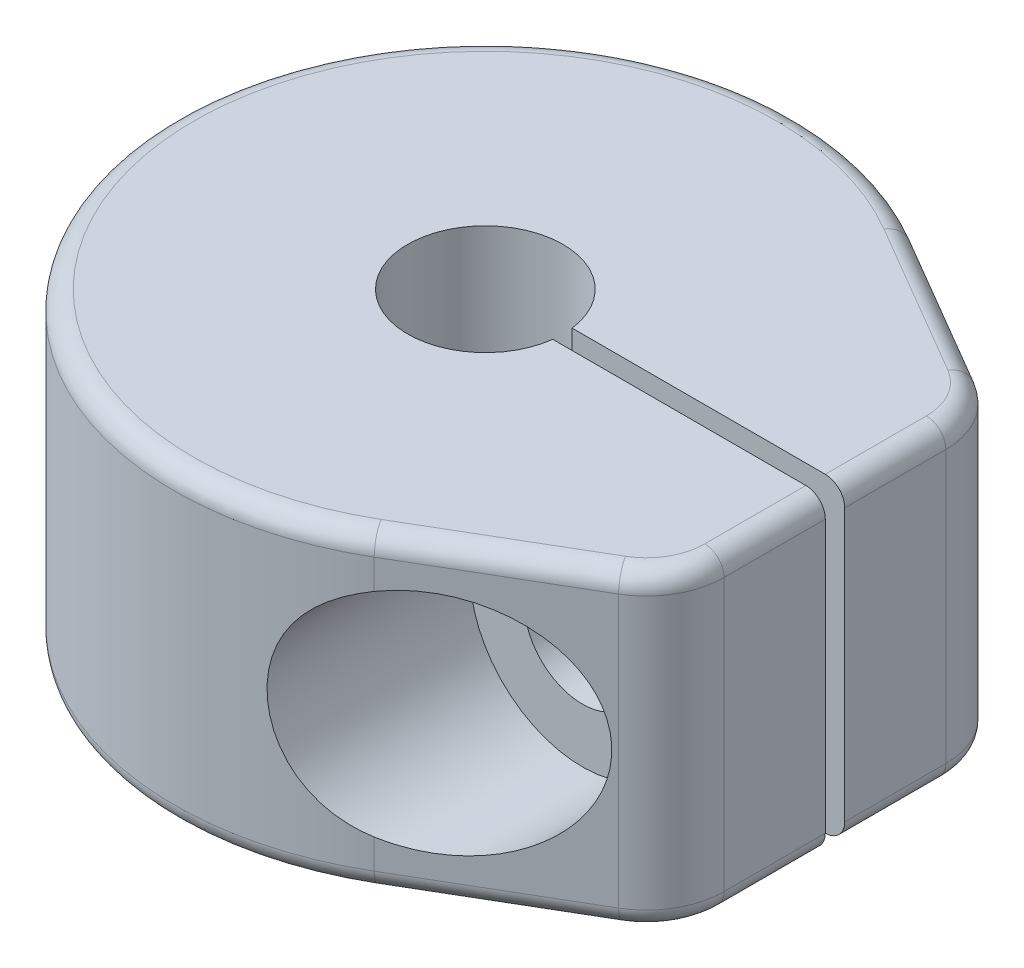
SolidWorks part; units mm, degrees
material "ABS"
ref_plane "Front" through (0, 0, 0) normal (0, 0, 1) x (1, 0, 0)
ref_plane "Top" through (0, 0, 0) normal (0, 1, 0) x (1, 0, 0)
ref_plane "Right" through (0, 0, 0) normal (1, 0, 0) x (0, 0, -1)
sketch "Esquisse1" plane through (0, 0, 0) normal (0, 1, 0) x (1, 0, 0)
  line L0 (4.043, 6.9032) -> (9, 4)
  line L1 (9, 4) -> (9, 0.25)
  line L2 (9, 0.25) -> (1.9843, 0.25)
  line L4 (-50, 0) -> (50, 0) construction
  line L5 (9, -0.25) -> (1.9843, -0.25)
  line L6 (9, -4) -> (9, -0.25)
  line L7 (4.043, -6.9032) -> (9, -4)
  arc A0 (4.043, 6.9032) -> (4.043, -6.9032) centre (0, 0) ccw
  arc A1 (1.9843, 0.25) -> (1.9843, -0.25) centre (0, 0) ccw
  dimension "D1" = 2
  dimension "D2" = 8
  dimension "D4" = 9
  dimension "D3" = 0.5
  dimension "D5" = 8
extrude "Boss.-Extru.1" add sketch "Esquisse1" along normal mid plane 8
sketch "Esquisse2" plane through (0, 0, 0) normal (0, 0, 1) x (1, 0, 0)
  line L0 (9, 4) -> (9, -4) construction
  circle A0 centre (5, 0) radius 1.5
  dimension "D1" = 4
  dimension "D2" = 3
extrude "Enlèv. mat.-Extru.1" cut sketch "Esquisse2" against normal through all both and the other way through all
sketch "Esquisse3" plane through (0, 0, 0) normal (0, 0, 1) x (1, 0, 0)
  line L1 (2.25, 1.5877) -> (2.25, -1.5877)
  line L2 (2.25, -1.5877) -> (5, -3.1754)
  line L3 (5, -3.1754) -> (7.75, -1.5877)
  line L4 (7.75, -1.5877) -> (7.75, 1.5877)
  line L5 (7.75, 1.5877) -> (5, 3.1754)
  line L6 (5, 3.1754) -> (2.25, 1.5877)
  circle A0 centre (5, 0) radius 2.75 construction
  circle A1 centre (5, 0) radius 1.5 construction
  dimension "D1" = 5.5
extrude "Enlèv. mat.-Extru.2" cut sketch "Esquisse3" against normal through all from offset 2.5 offset against normal yes
sketch "Esquisse4" plane through (0, 0, 0) normal (0, 0, 1) x (1, 0, 0)
  circle A0 centre (5, 0) radius 2.9
  circle A1 centre (5, 0) radius 1.5 construction
  dimension "D1" = 5.8
extrude "Enlèv. mat.-Extru.3" cut sketch "Esquisse4" along normal blind 8 from offset 2.5
fillet "Congé1" radius 2 2 edges at (9, 0, -4) (9, 0, 4)
fillet "Congé2" radius 0.5 14 edges at (9, -4, -1.5518) (8.7352, -4, -3.8482) (6.0269, -4, -5.7413) (-8, -4, 0) (6.0269, -4, 5.7413) (8.7352, -4, 3.8482) (9, 4, -1.5518) (8.7352, 4, -3.8482) (6.0269, 4, -5.7413) (-8, 4, 0) (6.0269, 4, 5.7413) (8.7352, 4, 3.8482) (9, -4, 1.5518) (9, 4, 1.5518)
sketch "Esquisse5" plane through (0, -4, 0) normal (0, -1, 0) x (1, 0, 0)
  circle A0 centre (1.1759, 0) radius 10.0979
extrude "Boss.-Extru.2" [suppressed] add sketch "Esquisse5" against normal blind 0.2
